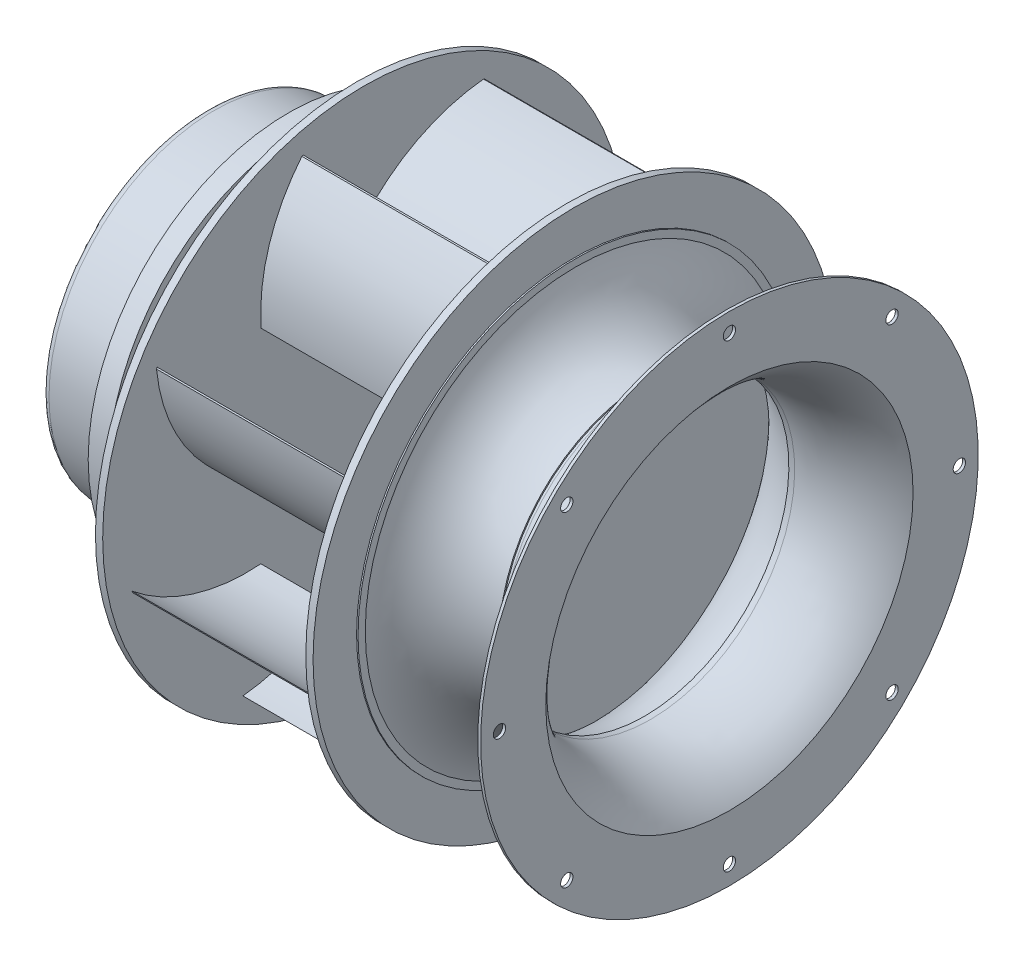
SolidWorks part; units mm, degrees
ref_plane "Front Plane" through (0, 0, 0) normal (0, 0, 1) x (1, 0, 0)
ref_plane "Top Plane" through (0, 0, 0) normal (0, 1, 0) x (1, 0, 0)
ref_plane "Right Plane" through (0, 0, 0) normal (1, 0, 0) x (0, 0, -1)
sketch "Sketch1" plane through (0, 0, 0) normal (0, 0, 1) x (1, 0, 0)
  line L0 (0, 0) -> (831.9083, 0) construction
  line L1 (0, 0) -> (0, 109)
  line L2 (5, 114) -> (56, 114)
  line L3 (56, 114) -> (56, 138)
  line L4 (56, 138) -> (69.9, 138)
  line L5 (69.9, 138) -> (69.9, 98)
  line L6 (69.9, 98) -> (74.9, 98)
  line L7 (74.9, 98) -> (74.9, 133)
  line L8 (74.9, 133) -> (84.9, 133)
  line L9 (84.9, 133) -> (84.9, 98)
  line L10 (84.9, 98) -> (103, 98)
  line L11 (103, 98) -> (103, 0)
  line L12 (103, 0) -> (0, 0)
  arc A0 (5, 114) -> (0, 109) centre (5, 109) ccw
  point P16 (0, 114)
  dimension "D10" = 5
  dimension "D1" = 114
  dimension "D2" = 24
  dimension "D3" = 56
  dimension "D4" = 40
  dimension "D5" = 35
  dimension "D6" = 5
  dimension "D7" = 13.9
  dimension "D8" = 10
  dimension "D9" = 47
revolve "Revolve1" add sketch "Sketch1" angle 360 about L0
sketch "Sketch2" plane through (103, 0, 0) normal (1, 0, 0) x (0, 0, -1)
  circle A0 centre (0, 0) radius 180
  dimension "D1" = 360
extrude "Extrude1" add sketch "Sketch2" along normal blind 5
sketch "Sketch9" plane through (103, 0, 0) normal (-1, 0, 0) x (0, 0, 1)
  circle A0 centre (0, 0) radius 175
  circle A1 centre (0, 0) radius 70
  circle A2 centre (0, 0) radius 180 construction
  dimension "D1" = 5
  dimension "D2" = 140
extrude "Extrude7" cut sketch "Sketch9" against normal blind 3
ref_plane "Plane1" through (248, 0, 0) normal (1, 0, 0) x (0, 0, -1)
sketch "Sketch3" plane through (248, 0, 0) normal (1, 0, 0) x (0, 0, -1)
  circle A0 centre (0, 0) radius 180
  dimension "D1" = 360
extrude "Extrude2" add sketch "Sketch3" along normal blind 5 separate body
sketch "Sketch4" plane through (108, 0, 0) normal (1, 0, 0) x (0, 0, -1)
  line L0 (0, 0) -> (0, 165) construction
  line L1 (0, 0) -> (90, 155.8846) construction
  line L2 (0, 100) -> (0.866, 99.5)
  line L3 (82.5, 142.8942) -> (83.366, 142.3942)
  circle A0 centre (0, 0) radius 165 construction
  circle A1 centre (0, 0) radius 180 construction
  circle A2 centre (0, 0) radius 100 construction
  arc A3 (0, 100) -> (82.5, 142.8942) centre (94.776, 18.4985) cw
  arc A4 (0.866, 99.5) -> (83.366, 142.3942) centre (95.6421, 17.9985) cw
  dimension "D1" = 15
  dimension "D2" = 200
  dimension "D6" = 125
  dimension "D7" = 125
  dimension "D3" = 30
  dimension "D4" = 60
  dimension "D5" = 1
extrude "Extrude3" add sketch "Sketch4" along normal up to surface (145 mm away) up to face at (253, 0, -180)
ref_axis "Axis1" through (253.5503, 0, 0) along (-1, 0, 0)
pattern_circular "CirPattern1" count 8 over 360 about axis through (253.5503, 0, 0) along (-1, 0, 0) of "Extrude3"
sketch "Sketch5" plane through (0, 0, 0) normal (0, 0, 1) x (1, 0, 0)
  line L0 (0, 0) -> (527.2916, 0) construction
  line L1 (253.5503, 0) -> (75.411, 0) construction
  line L2 (253, 150) -> (254, 150)
  line L3 (254, 150) -> (254, 145)
  line L4 (253, 150) -> (253, 145)
  line L5 (304, 102.5) -> (304, 101.5)
  line L6 (56, 138) -> (56, -138) construction
  line L7 (253, -180) -> (253, 180) construction
  arc A0 (254, 145) -> (304, 102.5) centre (311.5339, 162.0251) ccw
  arc A1 (253, 145) -> (304, 101.5) centre (310.7957, 161.1139) ccw
  dimension "D7" = 60
  dimension "D8" = 60
  dimension "D1" = 101.5
  dimension "D2" = 1
  dimension "D3" = 1
  dimension "D4" = 5
  dimension "D5" = 150
  dimension "D6" = 248
revolve "Revolve2" add sketch "Sketch5" angle 360 about L0
ref_plane "Plane3" through (360, 0, 0) normal (1, 0, 0) x (0, 0, -1)
sketch "Sketch6" plane through (0, 0, 0) normal (0, 0, 1) x (1, 0, 0)
  line L0 (360, 171.5) -> (358, 171.5)
  line L1 (360, -251.35) -> (360, 251.35) construction
  line L2 (358, 171.5) -> (358, 126.6)
  line L3 (0, 0) -> (615.1417, 0) construction
  line L4 (0, 114) -> (0, -114) construction
  line L5 (253.5503, 0) -> (75.411, 0) construction
  line L6 (360, 171.5) -> (360, 126.6)
  line L7 (301.5, 101.5) -> (305.5, 101.5)
  line L8 (301.5, 101.5) -> (301.5, 99.5)
  line L9 (301.5, 99.5) -> (305.5, 99.5)
  arc A0 (305.5, 101.5) -> (358, 126.6) centre (304.2884, 171.4895) ccw
  arc A1 (305.5, 99.5) -> (360, 126.6) centre (304.6827, 169.4952) ccw
  dimension "D7" = 70
  dimension "D8" = 70
  dimension "D1" = 171.5
  dimension "D2" = 2
  dimension "D3" = 126.6
  dimension "D4" = 58.5
  dimension "D5" = 101.5
  dimension "D6" = 4
revolve "Revolve3" add sketch "Sketch6" angle 360 about L3
sketch "Sketch7" plane through (360, 0, 0) normal (1, 0, 0) x (0, 0, -1)
  line L0 (0, 0) -> (0, 158.5) construction
  circle A0 centre (0, 0) radius 158.5 construction
  circle A1 centre (0, 158.5) radius 4.25
  dimension "D1" = 317
  dimension "D2" = 8.5
extrude "Extrude5" cut sketch "Sketch7" against normal blind 5
pattern_circular "CirPattern2" count 8 over 360 about axis through (253.5503, 0, 0) along (-1, 0, 0) of "Extrude5"
sketch "Sketch10" plane through (56, 0, 0) normal (-1, 0, 0) x (0, 0, 1)
  line L0 (0, 0) -> (-287.0199, 0) construction
  line L1 (0, 0) -> (0, 218.9031) construction
  circle A0 centre (0, 126) radius 5
  circle A1 centre (0, 0) radius 126 construction
  circle A2 centre (126, 0) radius 5
  circle A3 centre (0, -126) radius 5
  circle A4 centre (-126, 0) radius 5
  point P16 (0, 0)
  dimension "D1" = 10
  dimension "D2" = 252
  dimension "D3" = 4
extrude "Cut-Extrude1" cut sketch "Sketch10" against normal up to next (13.9 mm away)
